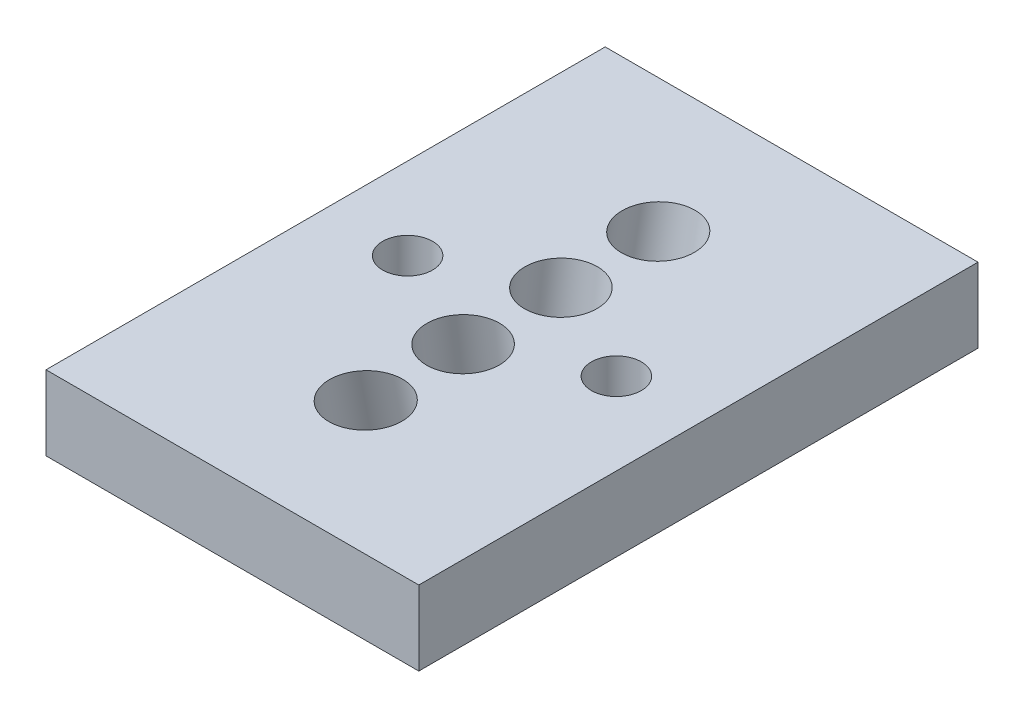
SolidWorks part; units mm, degrees
ref_plane "Front Plane" through (0, 0, 0) normal (0, 0, 1) x (1, 0, 0)
ref_plane "Top Plane" through (0, 0, 0) normal (0, 1, 0) x (1, 0, 0)
ref_plane "Right Plane" through (0, 0, 0) normal (1, 0, 0) x (0, 0, -1)
sketch "Sketch2" plane through (0, 0, 0) normal (0, 1, 0) x (1, 0, 0)
  line L1 (12.7, -19.05) -> (-12.7, -19.05)
  line L2 (12.7, -19.05) -> (12.7, 19.05)
  line L3 (12.7, 19.05) -> (-12.7, 19.05)
  line L4 (-12.7, -19.05) -> (-12.7, 19.05)
  line L5 (12.7, -19.05) -> (-12.7, 19.05) construction
  line L6 (12.7, 19.05) -> (-12.7, -19.05) construction
  point P0 (0, 0)
  dimension "D1" = 25.4
  dimension "D2" = 38.1
extrude "Boss-Extrude1" add sketch "Sketch2" along normal blind 5.08
sketch "Sketch6" plane through (12.7, 0, 0) normal (1, 0, 0) x (0, 0, -1)
  line L0 (-19.05, 124.7522) -> (-4.3561, 5.08) construction
  line L2 (-19.05, 5.08) -> (-19.05, 0) construction
  line L3 (-19.05, 5.08) -> (19.05, 5.08) construction
  line L4 (-4.3561, 5.08) -> (-4.3561, 22.1341) construction
  line L5 (-13.0683, 5.08) -> (-13.0683, 23.1616)
  line L6 (-13.0683, 5.08) -> (-16.6531, 23.776)
  dimension "D1" = 7
  dimension "D2" = 4.3561
  dimension "D3" = 5.9817
ref_plane "Plane3" through (12.7, 5.08, 4.3561) normal (0, -0.9925, -0.1219) x (-1, 0, 0)
sketch "Sketch7" plane through (12.7, 5.08, 4.3561) normal (0, -0.9925, -0.1219) x (-1, 0, 0)
  circle A0 centre (12.7, 1.016) radius 2.4638
extrude "Cut-Extrude1" cut sketch "Sketch7" along normal through all and the other way through all
ref_plane "Plane4" through (0, 0, 0) normal (0, 0, -1) x (-1, 0, 0)
ref_plane "Plane5" through (12.7, 5.08, 13.0683) normal (0, 0.9821, 0.1883) x (1, 0, 0)
sketch "Sketch16" plane through (12.7, 5.08, 13.0683) normal (0, 0.9821, 0.1883) x (1, 0, 0)
  circle A0 centre (-12.7, 3.048) radius 2.4638
extrude "Cut-Extrude2" cut sketch "Sketch16" against normal through all and the other way through all
mirror "Mirror2" about plane through (0, 0, 0) normal (0, 0, -1) of "Cut-Extrude1", "Cut-Extrude2"
hole_wizard "M3 Clearance Hole1" positions "Sketch21" profile "Sketch20" hole size "M3" standard "ANSI Metric"
sketch "Sketch21" plane through (0, 5.08, 0) normal (0, 1, 0) x (1, 0, 0)
  line L0 (2.794, 0) -> (-2.794, 0) construction
  line L1 (-12.7, 19.05) -> (-12.7, -19.05) construction
  line L2 (12.7, -19.05) -> (12.7, 19.05) construction
  point P0 (7.112, 0)
  point P4 (-7.112, 0)
  dimension "D1" = 5.588
  dimension "D2" = 5.588
sketch "Sketch20" plane through (7.112, 5.08, 0) normal (1, 0, 0) x (0, 0, 1)
  line L0 (0, 0) -> (0, 26.4215)
  line L1 (0, 26.4215) -> (1.7, 25.4)
  line L2 (1.7, 25.4) -> (1.7, 0)
  line L5 (1.7, 0) -> (0, 0)
  line L10 (0, 26.4215) -> (-1.7, 25.4) construction
  line L11 (0, -6.35) -> (0, 107.95) construction
  dimension "Hole Dia." = 3.4
  dimension "Hole Depth" = 25.4
  dimension "Drill Angle" = 118
sketch "Sketch17" plane through (0, 9.398, 0) normal (0, 1, 0) x (1, 0, 0)
  circle A0 centre (7.112, 0) radius 2.159
  circle A1 centre (-7.112, 0) radius 2.159
extrude "Cut-Extrude3" [suppressed] cut sketch "Sketch17" against normal through all
